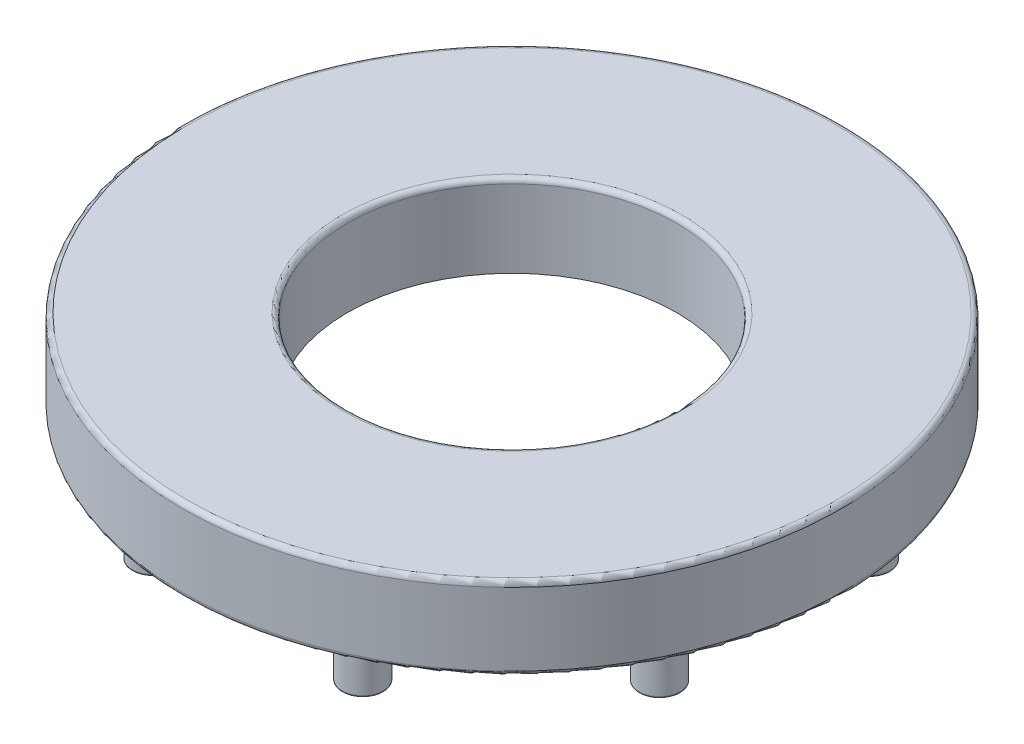
SolidWorks part; units mm, degrees
ref_plane "Front Plane" through (0, 0, 0) normal (0, 0, 1) x (1, 0, 0)
ref_plane "Top Plane" through (0, 0, 0) normal (0, 1, 0) x (1, 0, 0)
ref_plane "Right Plane" through (0, 0, 0) normal (1, 0, 0) x (0, 0, -1)
sketch "Sketch1" plane through (0, 0, 0) normal (0, 1, 0) x (1, 0, 0)
  line L0 (0, 0) -> (0, -1283.1794) construction
  line L1 (0, 0) -> (-770.4257, -1845.6555) construction
  line L2 (0, 0) -> (760.3023, -1849.8488) construction
  line L3 (-641.8116, -1537.5435) -> (1381.2039, -1537.5435) construction
  circle A0 centre (0, 0) radius 2000
  circle A1 centre (0, 0) radius 1100 construction
  circle A2 centre (0, 0) radius 1000
  circle A3 centre (-641.8116, -1537.5435) radius 125
  circle A4 centre (631.9424, -1537.5435) radius 125
  dimension "D1" = 4000
  dimension "D2" = 2000
  dimension "D3" = 2200
  dimension "D5" = 250
  dimension "D6" = 250
  dimension "D7" = 1273.754
  dimension "D4" = 45
extrude "Boss-Extrude2" add sketch "Sketch1" along normal blind 500
sketch "Sketch3" plane through (0, 0, 0) normal (0, -1, 0) x (1, 0, 0)
  circle A0 centre (631.9424, 1537.5435) radius 125
  circle A1 centre (-641.8116, 1537.5435) radius 125
  circle A2 centre (1537.5435, 641.8116) radius 125
  circle A3 centre (1537.5435, -631.9424) radius 125
  circle A4 centre (641.8116, -1537.5435) radius 125
  circle A5 centre (-631.9424, -1537.5435) radius 125
  circle A6 centre (-1537.5435, -641.8116) radius 125
  circle A7 centre (-1537.5435, 631.9424) radius 125
  point P21 (0, 0)
  dimension "D1" = 4
extrude "Boss-Extrude3" add sketch "Sketch1<6>" along normal blind 500 contours A3
sketch "Sketch1<6>" plane through (0, 0, 0) normal (0, 1, 0) x (1, 0, 0) same geometry as "Sketch1"
extrude "Boss-Extrude4" add sketch "Sketch1<7>" along normal blind 500 contours A4
sketch "Sketch1<7>" plane through (0, 0, 0) normal (0, 1, 0) x (1, 0, 0) same geometry as "Sketch1"
extrude "Boss-Extrude5" add sketch "Sketch3" along normal blind 350
fillet "Fillet1" radius 30 3 edges at (0, 0, 2000) (0, 500, 2000) (0, 500, 1000)
fillet "Fillet2" radius 10 8 edges at (-1537.5435, -350, 506.9424) (-1537.5435, -350, -766.8116) (-631.9424, -350, -1662.5435) (641.8116, -350, -1662.5435) (1537.5435, -350, -756.9424) (1537.5435, -350, 516.8116) (631.9424, -350, 1412.5435) (-641.8116, -350, 1412.5435)
